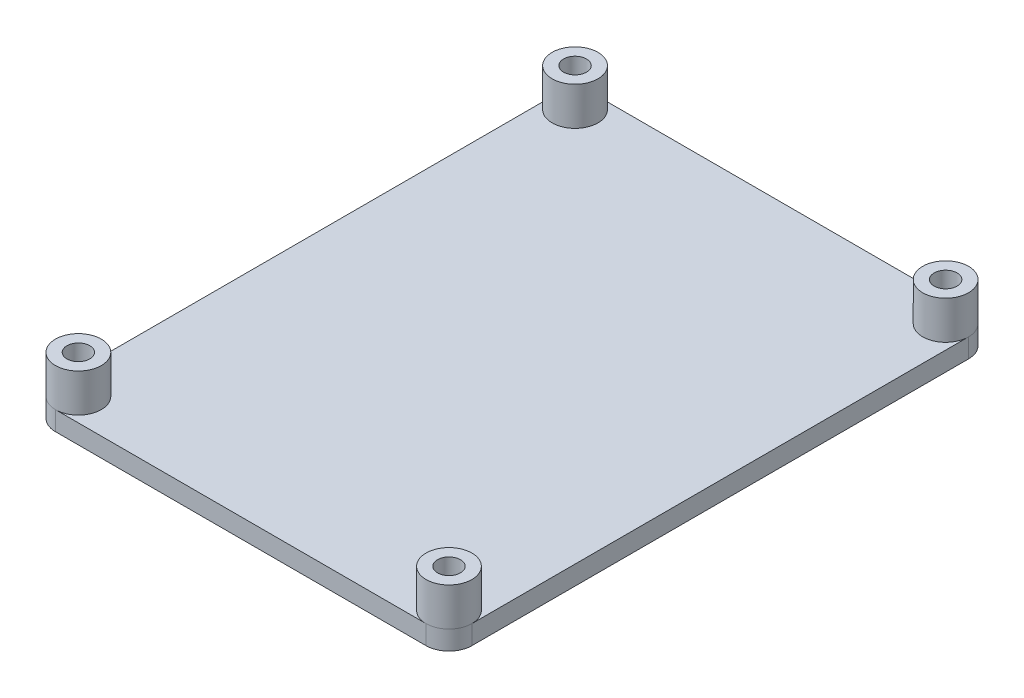
SolidWorks part; units mm, degrees
ref_plane "Front Plane" through (0, 0, 0) normal (0, 0, 1) x (1, 0, 0)
ref_plane "Top Plane" through (0, 0, 0) normal (0, 1, 0) x (1, 0, 0)
ref_plane "Right Plane" through (0, 0, 0) normal (1, 0, 0) x (0, 0, -1)
sketch "Sketch1" plane through (0, 0, 0) normal (0, 1, 0) x (1, 0, 0)
  line L1 (-70.0974, -15.775) -> (-15.5974, -15.775)
  line L2 (-70.0974, -15.775) -> (-70.0974, -86.775)
  line L3 (-70.0974, -86.775) -> (-15.5974, -86.775)
  line L4 (-15.5974, -15.775) -> (-15.5974, -86.775)
  dimension "D1" = 54.5
  dimension "D2" = 71
extrude "Boss-Extrude1" add sketch "Sketch1" along normal blind 2.5
sketch "Sketch2" plane through (0, 2.5, 0) normal (0, 1, 0) x (1, 0, 0)
  line L0 (-70.0974, -15.775) -> (-70.0974, -86.775) construction
  line L1 (-70.0974, -86.775) -> (-15.5974, -86.775) construction
  line L2 (-15.5974, -86.775) -> (-15.5974, -15.775) construction
  line L3 (-15.5974, -15.775) -> (-70.0974, -15.775) construction
  circle A0 centre (-67.0974, -18.775) radius 3
  circle A1 centre (-18.5974, -18.775) radius 3
  circle A2 centre (-18.5974, -83.775) radius 3
  circle A3 centre (-67.0974, -83.775) radius 3
  dimension "D1" = 6
  dimension "D2" = 6
  dimension "D3" = 6
  dimension "D4" = 6
  dimension "D5" = 3
  dimension "D6" = 3
  dimension "D7" = 3
  dimension "D8" = 3
  dimension "D9" = 3
  dimension "D10" = 3
  dimension "D11" = 3
  dimension "D12" = 3
extrude "Boss-Extrude2" add sketch "Sketch2" along normal blind 5
fillet "Fillet1" radius 3 4 edges at (-70.0974, 1.25, 15.775) (-15.5974, 1.25, 15.775) (-15.5974, 1.25, 86.775) (-70.0974, 1.25, 86.775)
sketch "Sketch3" plane through (0, 7.5, 0) normal (0, 1, 0) x (1, 0, 0)
  circle A0 centre (-67.0974, -18.775) radius 1.5
  circle A1 centre (-18.5974, -18.775) radius 1.5
  circle A2 centre (-18.5974, -83.775) radius 1.5
  circle A3 centre (-67.0974, -83.775) radius 1.5
  dimension "D1" = 3
  dimension "D2" = 3
  dimension "D3" = 3
  dimension "D4" = 3
extrude "Cut-Extrude1" cut sketch "Sketch3" against normal up to surface (7.5 mm away) up to face at (-42.8474, 0, 51.275)
